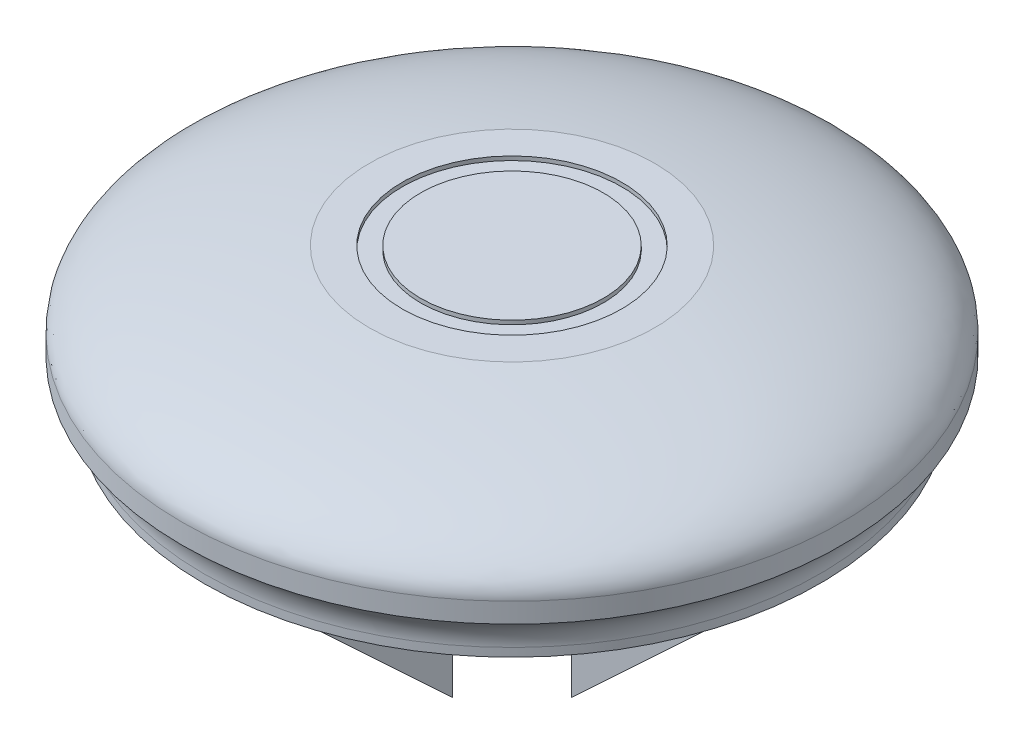
SolidWorks part; units mm, degrees
ref_plane "Front Plane" through (0, 0, 0) normal (0, 0, 1) x (1, 0, 0)
ref_plane "Top Plane" through (0, 0, 0) normal (0, 1, 0) x (1, 0, 0)
ref_plane "Right Plane" through (0, 0, 0) normal (1, 0, 0) x (0, 0, -1)
sketch "Sketch1" plane through (0, 0, 0) normal (0, 1, 0) x (1, 0, 0)
  line L0 (-59.9437, 50.8884) -> (-59.9437, 1.558)
  line L1 (-59.9437, 1.558) -> (-39.9437, 1.558)
  line L2 (-39.9437, 50.8884) -> (-39.9437, 1.558)
  line L3 (24.3866, -33.442) -> (-24.9437, -33.442)
  line L4 (24.3866, -13.442) -> (-24.9437, -13.442)
  line L5 (-24.9437, -13.442) -> (-24.9437, -33.442)
  line L6 (-59.9437, -97.7723) -> (-59.9437, -48.442)
  line L7 (-39.9437, -97.7723) -> (-39.9437, -48.442)
  line L8 (-39.9437, -48.442) -> (-59.9437, -48.442)
  line L9 (-124.2741, -13.442) -> (-74.9437, -13.442)
  line L10 (-124.2741, -33.442) -> (-74.9437, -33.442)
  line L11 (-74.9437, -33.442) -> (-74.9437, -13.442)
  arc A0 (-59.9437, 50.8884) -> (-124.2741, -13.442) centre (-49.9437, -23.442) ccw
  arc A1 (-124.2741, -33.442) -> (-59.9437, -97.7723) centre (-49.9437, -23.442) ccw
  arc A2 (-39.9437, -97.7723) -> (24.3866, -33.442) centre (-49.9437, -23.442) ccw
  arc A3 (24.3866, -13.442) -> (-39.9437, 50.8884) centre (-49.9437, -23.442) ccw
  circle A4 centre (-49.9437, -23.442) radius 82.8322
extrude "Boss-Extrude1" add sketch "Sketch1" along normal blind 5
ref_plane "Plane1" through (0, 0, 23.442) normal (0, 0, 1) x (1, 0, 0)
sketch "Sketch2" plane through (0, 0, 23.442) normal (0, 0, 1) x (1, 0, 0)
  line L0 (-49.9437, 5) -> (-49.9437, 25.9109)
  line L1 (32.8884, 5) -> (-132.7759, 5) construction
  line L2 (-49.9437, 5) -> (32.8884, 5)
  ellipse E0 centre (-49.9437, 5) end of major axis (32.8884, 5) minor radius 20.9109 (32.8884, 5) -> (-49.9437, 25.9109) ccw
revolve "Revolve1" add sketch "Sketch2" angle 360 about L0
sketch "Sketch3" plane through (0, 0, 23.442) normal (0, 0, 1) x (1, 0, 0)
  line L1 (-96.5274, 27.971) -> (-3.3601, 27.971)
  line L2 (-96.5274, 27.971) -> (-96.5274, 23.8509)
  line L3 (-96.5274, 23.8509) -> (-3.3601, 23.8509)
  line L4 (-3.3601, 27.971) -> (-3.3601, 23.8509)
  line L5 (-96.5274, 27.971) -> (-3.3601, 23.8509) construction
  line L6 (-96.5274, 23.8509) -> (-3.3601, 27.971) construction
  point P0 (-49.9437, 25.9109)
extrude "Cut-Extrude1" cut sketch "Sketch3" against normal mid plane 150
sketch "Sketch4" plane through (0, 23.8509, 0) normal (0, 1, 0) x (1, 0, 0)
  line L0 (-2.75, -23.442) -> (2.75, -23.442) construction
  circle A0 centre (-49.9437, -23.442) radius 22.9729
  circle A1 centre (-49.9437, -23.442) radius 27.5983
extrude "Cut-Extrude2" cut sketch "Sketch4" against normal blind 1
sketch "Sketch5" plane through (0, 0, 0) normal (0, -1, 0) x (1, 0, 0)
  line L0 (-59.9437, 97.7723) -> (-59.9437, 48.442)
  line L1 (-59.9437, 48.442) -> (-39.9437, 48.442)
  line L2 (-39.9437, 48.442) -> (-39.9437, 97.7723)
  line L3 (-24.9437, 33.442) -> (24.3866, 33.442)
  line L4 (24.3866, 13.442) -> (-24.9437, 13.442)
  line L5 (-24.9437, 13.442) -> (-24.9437, 33.442)
  line L6 (-74.9437, 33.442) -> (-74.9437, 13.442)
  line L7 (-74.9437, 13.442) -> (-124.2741, 13.442)
  line L8 (-74.9437, 33.442) -> (-124.2741, 33.442)
  line L9 (-59.9437, -1.558) -> (-39.9437, -1.558)
  line L10 (-39.9437, -1.558) -> (-39.9437, -50.8884)
  line L11 (-59.9437, -1.558) -> (-59.9437, -50.8884)
  arc A0 (-39.9437, -50.8884) -> (24.3866, 13.442) centre (-49.9437, 23.442) ccw
  arc A1 (-124.2741, 13.442) -> (-59.9437, -50.8884) centre (-49.9437, 23.442) ccw
  arc A2 (-59.9437, 97.7723) -> (-124.2741, 33.442) centre (-49.9437, 23.442) ccw
  arc A3 (24.3866, 33.442) -> (-39.9437, 97.7723) centre (-49.9437, 23.442) ccw
  circle A4 centre (-49.9437, 23.442) radius 77.4336
extrude "Boss-Extrude2" add sketch "Sketch5" along normal blind 11
fillet "Fillet1" radius 10 1 edges at (-49.9437, 0, 100.8756)
sketch "Sketch6" plane through (0, -11, 0) normal (0, -1, 0) x (1, 0, 0)
  line L1 (-24.9437, 33.442) -> (24.3866, 33.442)
  line L2 (-24.9437, 33.442) -> (-24.9437, 13.442)
  line L3 (-24.9437, 13.442) -> (24.3866, 13.442)
  line L4 (24.3866, 33.442) -> (24.3866, 13.442)
extrude "Boss-Extrude3" add sketch "Sketch6" along normal blind 46
sketch "Sketch7" plane through (0, 0, 33.442) normal (0, 0, 1) x (1, 0, 0)
  line L0 (24.3866, -11) -> (-24.9437, -57)
  line L1 (-24.9437, -57) -> (24.3866, -57)
  line L2 (24.3866, -57) -> (24.3866, -11)
extrude "Cut-Extrude3" cut sketch "Sketch7" against normal blind 46
pattern_circular "CirPattern1" count 4 over 360 about axis through (-49.9437, 5, 23.442) along (0, -1, 0) of "Boss-Extrude3", "Cut-Extrude3"
